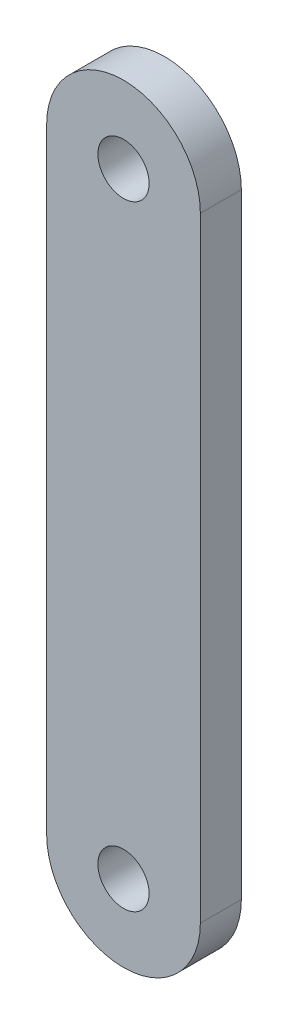
SolidWorks part; units mm, degrees
ref_plane "Front Plane" through (0, 0, 0) normal (0, 0, 1) x (1, 0, 0)
ref_plane "Top Plane" through (0, 0, 0) normal (0, 1, 0) x (1, 0, 0)
ref_plane "Right Plane" through (0, 0, 0) normal (1, 0, 0) x (0, 0, -1)
sketch "Sketch1" plane through (0, 0, 0) normal (0, 0, 1) x (1, 0, 0)
  line L0 (0, -19.05) -> (0, 19.05) construction
  line L1 (-4.7625, -19.05) -> (-4.7625, 19.05)
  line L2 (4.7625, -19.05) -> (4.7625, 19.05)
  arc A0 (-4.7625, -19.05) -> (4.7625, -19.05) centre (0, -19.05) ccw
  arc A1 (4.7625, 19.05) -> (-4.7625, 19.05) centre (0, 19.05) ccw
  circle A2 centre (0, 19.05) radius 1.5875
  circle A3 centre (0, -19.05) radius 1.5875
  point P3 (0, 0)
  dimension "D2" = 4.7625
  dimension "D3" = 3.175
  dimension "D1" = 38.1
extrude "Boss-Extrude1" add sketch "Sketch1" along normal blind 2.54
ref_axis "Axis1" through (0, -19.05, 2.54) along (0, 0, -1)
ref_axis "Axis2" through (0, 19.05, 2.54) along (0, 0, -1)
